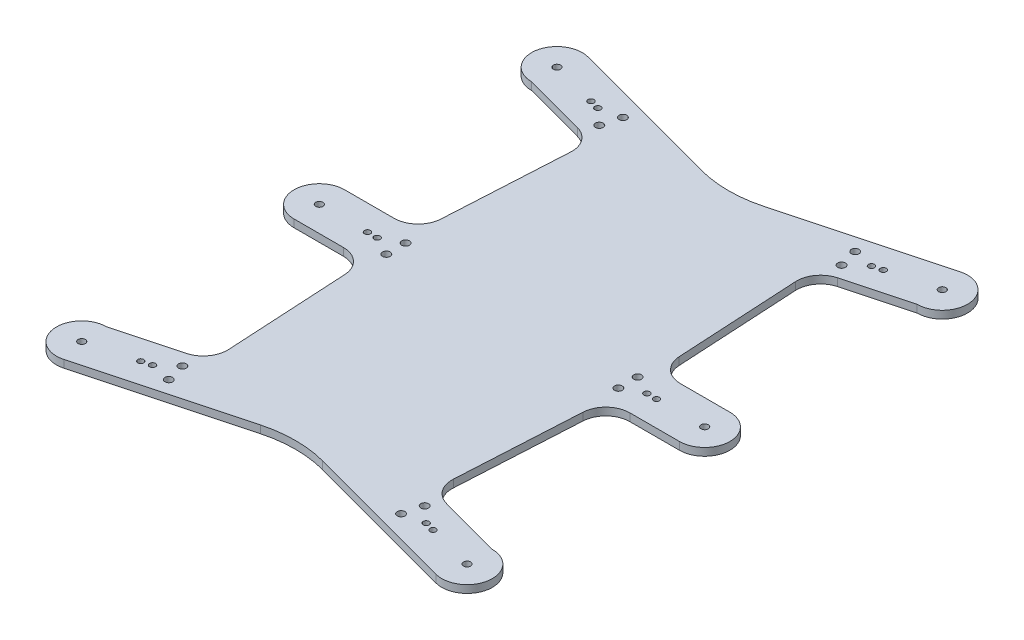
SolidWorks part; units mm, degrees
ref_plane "Front Plane" through (0, 0, 0) normal (0, 0, 1) x (1, 0, 0)
ref_plane "Top Plane" through (0, 0, 0) normal (0, 1, 0) x (1, 0, 0)
ref_plane "Right Plane" through (0, 0, 0) normal (1, 0, 0) x (0, 0, -1)
sketch "Sketch1" plane through (0, 0, 0) normal (0, 1, 0) x (1, 0, 0)
  line L0 (0, 32.1883) -> (0, -21.4181) construction
  line L1 (0, 0) -> (27.1703, 0) construction
  line L2 (-80, 10.5) -> (-50, 10.5)
  line L3 (-50, 10.5) -> (-46.1926, 79.0959)
  line L4 (-46.1926, 79.0959) -> (-80, 88.1546)
  line L5 (-77.2824, 108.7968) -> (0, 88.0891)
  line L6 (77.2824, 108.7968) -> (0, 88.0891)
  line L7 (46.1926, 79.0959) -> (80, 88.1546)
  line L8 (50, 10.5) -> (46.1926, 79.0959)
  line L9 (80, 10.5) -> (50, 10.5)
  line L10 (80, -10.5) -> (50, -10.5)
  line L11 (50, -10.5) -> (46.1926, -79.0959)
  line L12 (46.1926, -79.0959) -> (80, -88.1546)
  line L13 (77.2824, -108.7968) -> (0, -88.0891)
  line L14 (-77.2824, -108.7968) -> (0, -88.0891)
  line L15 (-46.1926, -79.0959) -> (-80, -88.1546)
  line L16 (-50, -10.5) -> (-46.1926, -79.0959)
  line L17 (-80, -10.5) -> (-50, -10.5)
  arc A0 (-80, 10.5) -> (-80, -10.5) centre (-80, 0) ccw
  arc A1 (-77.2824, 108.7968) -> (-80, 88.1546) centre (-80, 98.6546) ccw
  circle A2 centre (-80, 98.6546) radius 1.5
  circle A3 centre (-80, 0) radius 1.5
  circle A4 centre (80, 0) radius 1.5
  circle A5 centre (80, 98.6546) radius 1.5
  arc A6 (77.2824, 108.7968) -> (80, 88.1546) centre (80, 98.6546) cw
  arc A7 (80, 10.5) -> (80, -10.5) centre (80, 0) cw
  arc A8 (77.2824, -108.7968) -> (80, -88.1546) centre (80, -98.6546) ccw
  circle A9 centre (80, -98.6546) radius 1.5
  circle A10 centre (-80, -98.6546) radius 1.5
  arc A11 (-77.2824, -108.7968) -> (-80, -88.1546) centre (-80, -98.6546) cw
  circle A12 centre (50.2947, -86.554) radius 1.6 construction
  circle A13 centre (48.2241, -94.2814) radius 1.6 construction
  circle A14 centre (48.175, -4) radius 1.6 construction
  circle A15 centre (50.2947, -86.554) radius 1.6
  circle A16 centre (48.2241, -94.2814) radius 1.6
  circle A17 centre (48.175, -4) radius 1.6
  circle A18 centre (48.175, 4) radius 1.6
  circle A19 centre (50.2947, 86.554) radius 1.6
  circle A20 centre (48.2241, 94.2814) radius 1.6
  circle A21 centre (-50.2947, 86.554) radius 1.6
  circle A22 centre (-48.2241, 94.2814) radius 1.6
  circle A23 centre (-48.175, 4) radius 1.6
  circle A24 centre (-48.175, -4) radius 1.6
  circle A25 centre (-50.2947, -86.554) radius 1.6
  circle A26 centre (-48.2241, -94.2814) radius 1.6
  dimension "D2" = 10.5
  dimension "D3" = 3
  dimension "D1" = 75
  dimension "D4" = 80
  dimension "D5" = 30
  dimension "D6" = 35
  dimension "D7" = 68.5959
extrude "Boss-Extrude1" add sketch "Sketch1" along normal blind 3.175
sketch "Sketch2" plane through (0, 3.175, 0) normal (0, 1, 0) x (1, 0, 0)
  arc A0 (55.6104, -92.1194) -> (58.0252, -92.7665) centre (56.8178, -92.4429) ccw construction
  arc A1 (58.0252, -92.7665) -> (55.6104, -92.1194) centre (56.8178, -92.4429) ccw construction
  arc A2 (61.8889, -93.8017) -> (59.4741, -93.1547) centre (60.6815, -93.4782) ccw construction
  arc A3 (59.4741, -93.1547) -> (61.8889, -93.8017) centre (60.6815, -93.4782) ccw construction
  arc A4 (54.75, 0) -> (57.25, 0) centre (56, 0) ccw construction
  arc A5 (57.25, 0) -> (54.75, 0) centre (56, 0) ccw construction
  arc A6 (61.25, 0) -> (58.75, 0) centre (60, 0) ccw construction
  arc A7 (58.75, 0) -> (61.25, 0) centre (60, 0) ccw construction
  arc A8 (58.0252, 92.7665) -> (55.6104, 92.1194) centre (56.8178, 92.4429) ccw construction
  arc A9 (55.6104, 92.1194) -> (58.0252, 92.7665) centre (56.8178, 92.4429) ccw construction
  arc A10 (61.8889, 93.8017) -> (59.4741, 93.1547) centre (60.6815, 93.4782) ccw construction
  arc A11 (59.4741, 93.1547) -> (61.8889, 93.8017) centre (60.6815, 93.4782) ccw construction
  arc A12 (-59.4741, 93.1547) -> (-61.8889, 93.8017) centre (-60.6815, 93.4782) ccw construction
  arc A13 (-61.8889, 93.8017) -> (-59.4741, 93.1547) centre (-60.6815, 93.4782) ccw construction
  arc A14 (-58.0252, 92.7665) -> (-55.6104, 92.1194) centre (-56.8178, 92.4429) ccw construction
  arc A15 (-55.6104, 92.1194) -> (-58.0252, 92.7665) centre (-56.8178, 92.4429) ccw construction
  arc A16 (-58.75, 0) -> (-61.25, 0) centre (-60, 0) ccw construction
  arc A17 (-61.25, 0) -> (-58.75, 0) centre (-60, 0) ccw construction
  arc A18 (-57.25, 0) -> (-54.75, 0) centre (-56, 0) ccw construction
  arc A19 (-54.75, 0) -> (-57.25, 0) centre (-56, 0) ccw construction
  arc A20 (-58.0252, -92.7665) -> (-55.6104, -92.1194) centre (-56.8178, -92.4429) ccw construction
  arc A21 (-55.6104, -92.1194) -> (-58.0252, -92.7665) centre (-56.8178, -92.4429) ccw construction
  arc A22 (-59.4741, -93.1547) -> (-61.8889, -93.8017) centre (-60.6815, -93.4782) ccw construction
  arc A23 (-61.8889, -93.8017) -> (-59.4741, -93.1547) centre (-60.6815, -93.4782) ccw construction
  arc A24 (55.6104, -92.1194) -> (58.0252, -92.7665) centre (56.8178, -92.4429) ccw
  arc A25 (58.0252, -92.7665) -> (55.6104, -92.1194) centre (56.8178, -92.4429) ccw
  arc A26 (61.8889, -93.8017) -> (59.4741, -93.1547) centre (60.6815, -93.4782) ccw
  arc A27 (59.4741, -93.1547) -> (61.8889, -93.8017) centre (60.6815, -93.4782) ccw
  arc A28 (54.75, 0) -> (57.25, 0) centre (56, 0) ccw
  arc A29 (57.25, 0) -> (54.75, 0) centre (56, 0) ccw
  arc A30 (61.25, 0) -> (58.75, 0) centre (60, 0) ccw
  arc A31 (58.75, 0) -> (61.25, 0) centre (60, 0) ccw
  arc A32 (58.0252, 92.7665) -> (55.6104, 92.1194) centre (56.8178, 92.4429) ccw
  arc A33 (55.6104, 92.1194) -> (58.0252, 92.7665) centre (56.8178, 92.4429) ccw
  arc A34 (61.8889, 93.8017) -> (59.4741, 93.1547) centre (60.6815, 93.4782) ccw
  arc A35 (59.4741, 93.1547) -> (61.8889, 93.8017) centre (60.6815, 93.4782) ccw
  arc A36 (-59.4741, 93.1547) -> (-61.8889, 93.8017) centre (-60.6815, 93.4782) ccw
  arc A37 (-61.8889, 93.8017) -> (-59.4741, 93.1547) centre (-60.6815, 93.4782) ccw
  arc A38 (-58.0252, 92.7665) -> (-55.6104, 92.1194) centre (-56.8178, 92.4429) ccw
  arc A39 (-55.6104, 92.1194) -> (-58.0252, 92.7665) centre (-56.8178, 92.4429) ccw
  arc A40 (-58.75, 0) -> (-61.25, 0) centre (-60, 0) ccw
  arc A41 (-61.25, 0) -> (-58.75, 0) centre (-60, 0) ccw
  arc A42 (-57.25, 0) -> (-54.75, 0) centre (-56, 0) ccw
  arc A43 (-54.75, 0) -> (-57.25, 0) centre (-56, 0) ccw
  arc A44 (-58.0252, -92.7665) -> (-55.6104, -92.1194) centre (-56.8178, -92.4429) ccw
  arc A45 (-55.6104, -92.1194) -> (-58.0252, -92.7665) centre (-56.8178, -92.4429) ccw
  arc A46 (-59.4741, -93.1547) -> (-61.8889, -93.8017) centre (-60.6815, -93.4782) ccw
  arc A47 (-61.8889, -93.8017) -> (-59.4741, -93.1547) centre (-60.6815, -93.4782) ccw
extrude "Cut-Extrude1" cut sketch "Sketch2" against normal through all
fillet "Fillet1" radius 50 2 edges at (0, 1.5875, -88.0891) (0, 1.5875, 88.0891)
fillet "Fillet2" radius 10 8 edges at (46.1926, 1.5875, 79.0959) (50, 1.5875, 10.5) (50, 1.5875, -10.5) (46.1926, 1.5875, -79.0959) (-46.1926, 1.5875, -79.0959) (-50, 1.5875, -10.5) (-50, 1.5875, 10.5) (-46.1926, 1.5875, 79.0959)
